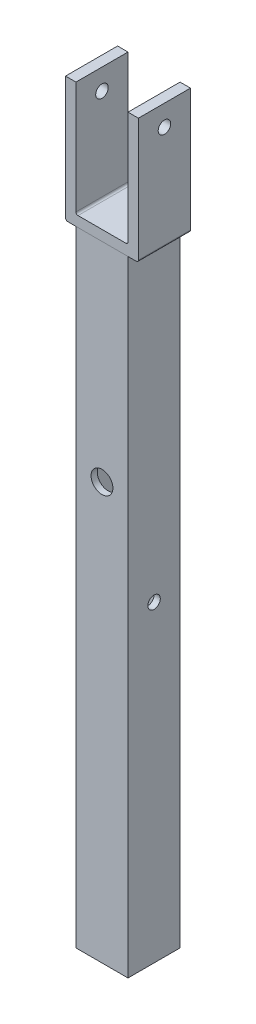
SolidWorks part; units mm, degrees
other "DetailItem2"
other "DetailItem3"
other "Weld Folder"
other "Weld Bead3"
other "Weld Bead2"
ref_plane "Front Plane" through (0, 0, 0) normal (0, 0, 1) x (1, 0, 0)
ref_plane "Top Plane" through (0, 0, 0) normal (0, 1, 0) x (1, 0, 0)
ref_plane "Right Plane" through (0, 0, 0) normal (1, 0, 0) x (0, 0, -1)
sketch "Sketch1" plane through (0, 0, 0) normal (0, 1, 0) x (1, 0, 0)
  line L15 (12.5, 12.5) -> (-12.5, 12.5)
  line L16 (12.5, 12.5) -> (12.5, -12.5)
  line L17 (12.5, -12.5) -> (-12.5, -12.5)
  line L18 (-12.5, 12.5) -> (-12.5, -12.5)
  line L19 (12.5, 12.5) -> (-12.5, -12.5) construction
  line L20 (12.5, -12.5) -> (-12.5, 12.5) construction
  line L21 (-9.5, 9.5) -> (9.5, 9.5)
  line L22 (-9.5, 9.5) -> (-9.5, -9.5)
  line L23 (-9.5, -9.5) -> (9.5, -9.5)
  line L24 (9.5, 9.5) -> (9.5, -9.5)
  line L25 (-9.5, 9.5) -> (9.5, -9.5) construction
  line L26 (-9.5, -9.5) -> (9.5, 9.5) construction
  point P0 (0, 0)
  point P6 (0, 0)
  dimension "D1" = 19
  dimension "D2" = 19
  dimension "D3" = 25
  dimension "D4" = 25
extrude "Boss-Extrude1" add sketch "Sketch1" along normal blind 300
sketch "Sketch2" plane through (0, 0, -12.5) normal (0, 0, -1) x (-1, 0, 0)
  line L0 (0, 0) -> (0, 200)
  line L1 (-12.5, 0) -> (12.5, 0) construction
  circle A0 centre (0, 200) radius 7.5
  dimension "D2" = 15
  dimension "D1" = 200
extrude "Cut-Extrude1" cut sketch "Sketch2" against normal blind 3 contours A0
sketch "Sketch3" plane through (0, 0, 12.5) normal (0, 0, 1) x (1, 0, 0)
  line L0 (0, 0) -> (0, 200)
  line L1 (-12.5, 0) -> (12.5, 0) construction
  circle A0 centre (0, 200) radius 5.25
  dimension "D1" = 10.5
extrude "Cut-Extrude2" cut sketch "Sketch3" against normal blind 3 contours A0
sketch "Sketch4" plane through (12.5, 0, 0) normal (1, 0, 0) x (0, 0, -1)
  line L0 (0, 0) -> (0, 150)
  line L1 (-12.5, 0) -> (12.5, 0) construction
  circle A0 centre (0, 150) radius 3
  dimension "D2" = 6
  dimension "D1" = 150
extrude "Cut-Extrude3" cut sketch "Sketch4" against normal blind 25 contours A0
sketch "Sketch5" plane through (0, 300, 0) normal (0, 1, 0) x (1, 0, 0)
  line L1 (17.5, 12.5) -> (-17.5, 12.5)
  line L2 (17.5, 12.5) -> (17.5, -12.5)
  line L3 (17.5, -12.5) -> (-17.5, -12.5)
  line L4 (-17.5, 12.5) -> (-17.5, -12.5)
  line L5 (17.5, 12.5) -> (-17.5, -12.5) construction
  line L6 (17.5, -12.5) -> (-17.5, 12.5) construction
  point P0 (0, 0)
  dimension "D1" = 25
  dimension "D2" = 35
extrude "Boss-Extrude2" add sketch "Sketch5" along normal blind 60 separate body
sketch "Sketch6" plane through (0, 360, 0) normal (0, 1, 0) x (1, 0, 0)
sketch "Sketch7" plane through (0, 360, 0) normal (0, 1, 0) x (1, 0, 0)
  line L0 (17.5, 12.5) -> (-17.5, 12.5) construction
  line L1 (12.5, -12.5) -> (-12.5, -12.5)
  line L2 (12.5, -12.5) -> (12.5, 12.5)
  line L3 (12.5, 12.5) -> (-12.5, 12.5)
  line L4 (-12.5, -12.5) -> (-12.5, 12.5)
  line L5 (12.5, -12.5) -> (-12.5, 12.5) construction
  line L6 (12.5, 12.5) -> (-12.5, -12.5) construction
  point P0 (0, 0)
extrude "Cut-Extrude4" cut sketch "Sketch7" against normal blind 55
sketch "Sketch8" plane through (-17.5, 0, 0) normal (-1, 0, 0) x (0, 0, 1)
  line L0 (0, 360) -> (0, 350)
  line L1 (-12.5, 360) -> (12.5, 360) construction
  circle A0 centre (0, 350) radius 3
  dimension "D2" = 6
  dimension "D1" = 10
extrude "Cut-Extrude5" cut sketch "Sketch8" against normal blind 55 contours A0
fillet "Fillet1" radius 1 2 edges at (12.5, 305, 0) (-12.5, 305, 0)
fillet "Fillet2" radius 1 2 edges at (17.5, 300, 0) (-17.5, 300, 0)
